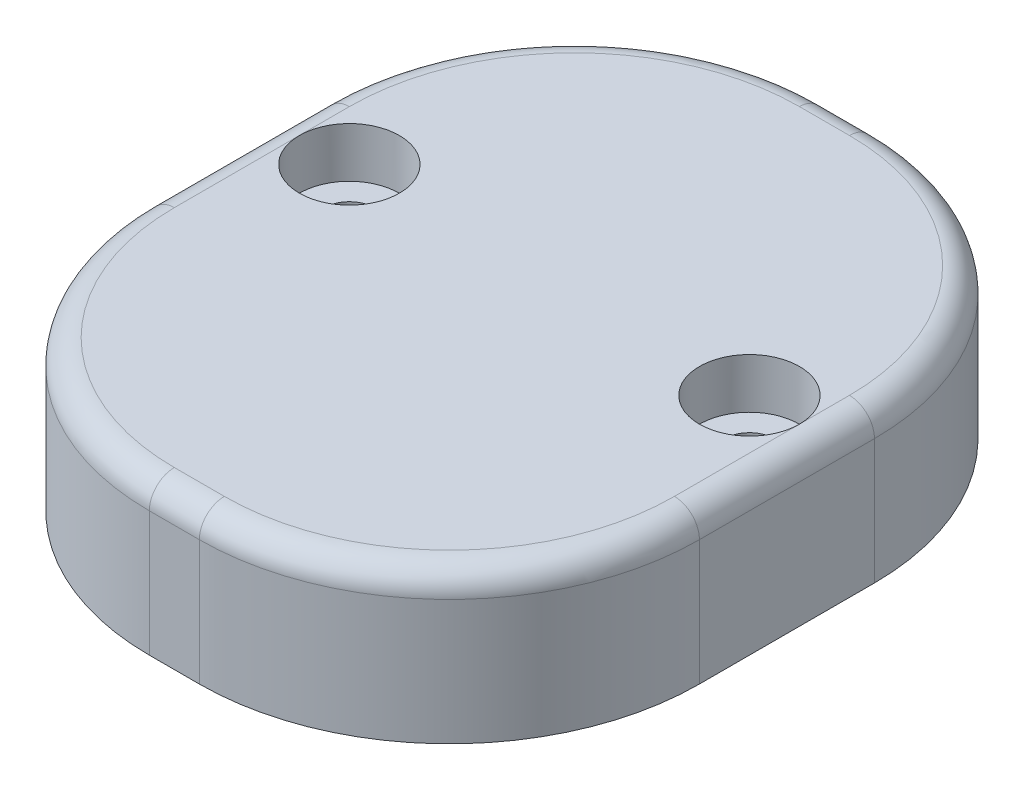
SolidWorks part; units mm, degrees
ref_plane "Plan de face" through (0, 0, 0) normal (0, 0, 1) x (1, 0, 0)
ref_plane "Plan de dessus" through (0, 0, 0) normal (0, 1, 0) x (1, 0, 0)
ref_plane "Plan de droite" through (0, 0, 0) normal (1, 0, 0) x (0, 0, -1)
sketch "Esquisse1" plane through (0, 0, 0) normal (0, 0, 1) x (1, 0, 0)
  line L1 (0, 0) -> (22, 0)
  line L2 (0, 0) -> (0, 6)
  line L3 (0, 6) -> (22, 6)
  line L4 (22, 0) -> (22, 6)
  arc A0 (6, 0) -> (16, 0) centre (11, 0) cw
  dimension "D3" = 5
  dimension "D1" = 6
  dimension "D2" = 22
  dimension "D4" = 11
extrude "Boss.-Extru.1" add sketch "Esquisse1" along normal blind 22 contours L1 A0 L4 L3 L2 region at (0.228, 3, 0)
sketch "Esquisse2" plane through (0, 0, 22) normal (0, 0, 1) x (1, 0, 0)
  line L1 (0, 0) -> (22, 0)
  line L2 (0, 0) -> (0, 6)
  line L3 (0, 6) -> (22, 6)
  line L4 (22, 0) -> (22, 6)
extrude "Boss.-Extru.2" add sketch "Esquisse2" along normal blind 5
hole_wizard "Chambrage pour vis à tête hexagonale M21" positions "Esquisse3" profile "Esquisse4" counterbore size "M2" standard "ISO" end condition through all
sketch "Esquisse3" plane through (0, 6, 0) normal (0, 1, 0) x (1, 0, 0)
  line L0 (11, -31.2926) -> (11, 8.1795) construction
  line L2 (0, -27) -> (0, 0) construction
  line L4 (0, 0) -> (22, 0) construction
  point P0 (19, -12)
  point P2 (3, -12)
  dimension "D1" = 16
  dimension "D2" = 11
  dimension "D3" = 8
  dimension "D4" = 12
  dimension "D5" = 12
sketch "Esquisse4" plane through (19, 6, 12) normal (1, 0, 0) x (0, 0, 1)
  line L0 (0, 0) -> (0, 6)
  line L1 (0, 6) -> (1, 6)
  line L3 (1, 6) -> (1, 2)
  line L4 (1, 2) -> (2, 2)
  line L5 (2, 2) -> (2, 0)
  line L7 (2, 0) -> (0, 0)
  line L11 (0, -6.35) -> (0, 107.95) construction
  dimension "Diamètre du perçage jusqu'au prochain" = 2
  dimension "Profondeur du perçage jusqu'au prochain" = 6
  dimension "Diamètre du chambrage" = 4
  dimension "Profondeur du chambrage" = 2
fillet "Congé1" radius 10 4 edges at (0, 3, 0) (0, 3, 27) (22, 3, 0) (22, 3, 27)
fillet "Congé2" radius 1 8 edges at (22, 6, 13.5) (19.0711, 6, 2.9289) (11, 6, 0) (2.9289, 6, 2.9289) (0, 6, 13.5) (2.9289, 6, 24.0711) (11, 6, 27) (19.0711, 6, 24.0711)
